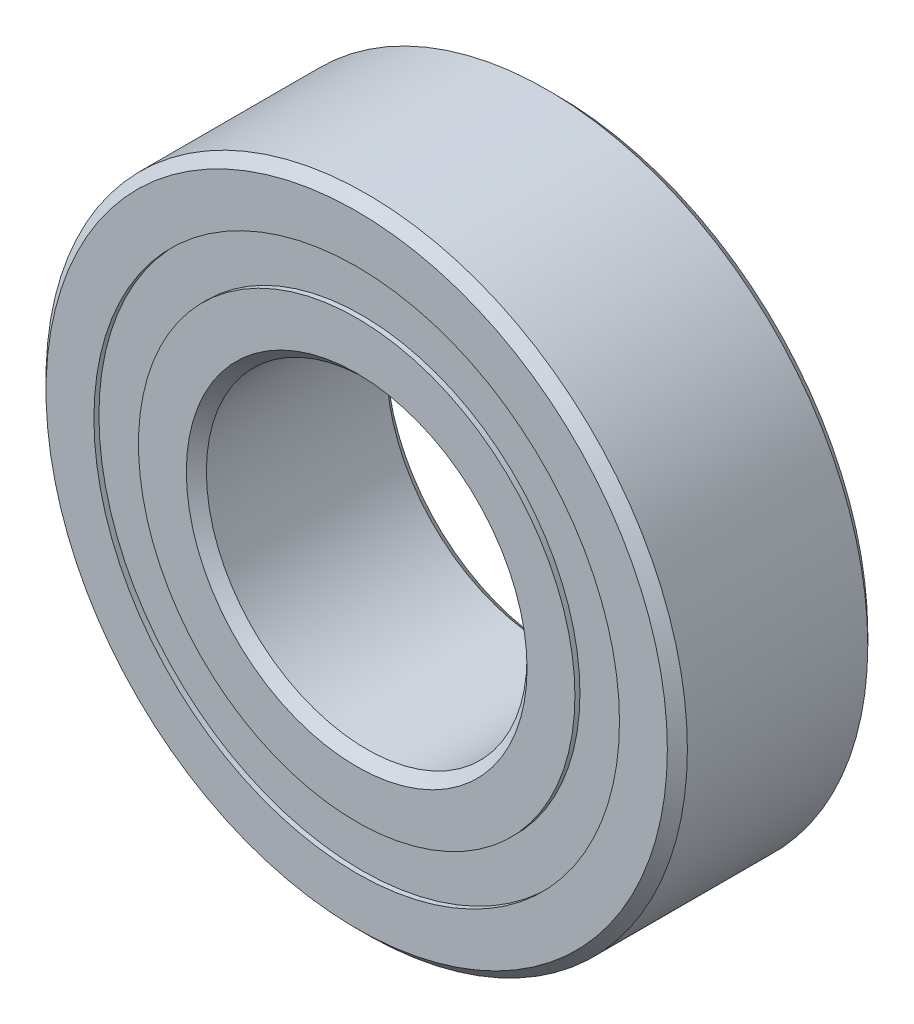
SolidWorks part; units mm, degrees
ref_plane "Front Plane" through (0, 0, 0) normal (0, 0, 1) x (1, 0, 0)
ref_plane "Top Plane" through (0, 0, 0) normal (0, 1, 0) x (1, 0, 0)
ref_plane "Right Plane" through (0, 0, 0) normal (1, 0, 0) x (0, 0, -1)
sketch "Sketch1" plane through (0, 0, 0) normal (1, 0, 0) x (0, 0, -1)
  line L0 (-2.5, 0) -> (2.5, 0) construction
  line L1 (0, 8) -> (0, -8) construction
  line L2 (2.25, 8) -> (-2.25, 8)
  line L3 (-2.25, 8) -> (-2.5, 7.75)
  line L4 (-2.5, 7.75) -> (-2.5, 6.5556)
  line L5 (-2.5, 6.5556) -> (-1.1111, 6.5556)
  line L6 (2.5, 6.5556) -> (1.1111, 6.5556)
  line L7 (2.5, 7.75) -> (2.5, 6.5556)
  line L8 (2.25, 8) -> (2.5, 7.75)
  line L9 (0, 8) -> (0, 6) construction
  line L10 (0, 6) -> (0, 4) construction
  arc A0 (-1.1111, 6.5556) -> (1.1111, 6.5556) centre (0, 6) cw
  arc A1 (-1.1111, 6.5556) -> (1.1111, 6.5556) centre (0, 6) ccw construction
  point P14 (0, 4)
  point P15 (0, -4)
  dimension "Width" = 5
  dimension "OD" = 16
  dimension "D1" = 45
  dimension "D2" = 0.25
  dimension "D3" = 2.2222
  dimension "Shaft Dia" = 8
  dimension "D4" = 0.5556
revolve "Revolve1" add sketch "Sketch1" angle 360 about L0
sketch "Sketch2" plane through (0, 0, 0) normal (1, 0, 0) x (0, 0, -1)
  line L0 (-2.5, 5.4444) -> (-1.1111, 5.4444)
  line L1 (-2.5, 7.75) -> (-2.5, -7.75) construction
  line L2 (-2.5, 5.4444) -> (-2.5, 4.25)
  line L3 (-2.5, 4.25) -> (-2.25, 4)
  line L4 (-2.25, 4) -> (2.25, 4)
  line L5 (0, 8) -> (0, -8) construction
  line L6 (0, 4) -> (0, 4.7577) construction
  line L7 (0, 4.7577) -> (0, 4) construction
  line L8 (-2.5, 5.4444) -> (-2.5, 3.0556) construction
  line L10 (2.5, 5.4444) -> (1.1111, 5.4444)
  line L11 (2.5, 5.4444) -> (2.5, 4.25)
  line L12 (2.5, 4.25) -> (2.25, 4)
  arc A0 (-1.1111, 5.4444) -> (1.1111, 5.4444) centre (0, 6) ccw
  arc A1 (1.1111, 6.5556) -> (-1.1111, 6.5556) centre (0, 6) ccw construction
  circle A2 centre (0, 6) radius 1.2423 construction
  dimension "D1" = 0.25
  dimension "D2" = 45
revolve "Revolve2" add sketch "Sketch2" angle 360 about L0
sketch "Sketch3" plane through (0, 0, 0) normal (1, 0, 0) x (0, 0, -1)
  line L0 (-1.2423, 6) -> (1.2423, 6)
  line L1 (0, 6) -> (0, 0) construction
  circle A1 centre (0, 6) radius 1.2423 construction
  arc A2 (-1.2423, 6) -> (1.2423, 6) centre (0, 6) cw
  arc A3 (1.1111, 6.5556) -> (-1.1111, 6.5556) centre (0, 6) ccw construction
  dimension "D1" = 2.4845
  dimension "D2" = 6
revolve "Revolve3" add sketch "Sketch3" angle 360 about L0
ref_axis "Axis1" through (0, 0, -2.5) along (0, 0, 1)
pattern_circular "CirPattern1" count 14 every 25.714 about axis through (0, 0, -2.5) along (0, 0, 1) of bodies 104
sketch "Sketch5" plane through (0, 0, 0) normal (1, 0, 0) x (0, 0, -1)
  line L0 (-2.5, 5.4444) -> (-1.1111, 5.4444) construction
  line L1 (-2.375, 6.5556) -> (-1.2423, 6.5556)
  line L2 (-2.375, 6.5556) -> (-2.375, 5.4444)
  line L3 (-2.375, 5.4444) -> (-1.2423, 5.4444)
  line L4 (-1.2423, 6.5556) -> (-1.2423, 5.4444)
  line L5 (1.2423, 6.5556) -> (2.375, 6.5556)
  line L6 (1.2423, 6.5556) -> (1.2423, 5.4444)
  line L7 (1.2423, 5.4444) -> (2.375, 5.4444)
  line L8 (2.375, 6.5556) -> (2.375, 5.4444)
  line L9 (-2.5, 6.5556) -> (-1.1111, 6.5556) construction
  line L10 (-2.375, 7.875) -> (-2.375, 6.5556) construction
  line L11 (-2.25, 8) -> (-2.5, 7.75) construction
  circle A0 centre (0, 6) radius 1.2423 construction
revolve "Revolve5" add sketch "Sketch5" angle 360 about L0
sketch "Sketch6" plane through (0, 0, 0) normal (0, 1, 0) x (1, 0, 0)
  point P0 (8, -2.5)
  point P1 (8, 2.5)
ref_axis "Center Axis 1" through (0, 0, -4.1209) along (0, 0, 1)
ref_plane "Contact Plane 1" through (0, 0, 2.5) normal (0, 0, 1) x (1, 0, 0)
ref_plane "Contact Plane 2" through (0, 0, -2.5) normal (0, 0, -1) x (-1, 0, 0)
equation "\"D2@Sketch1\" = \"Width@Sketch1\"*.05"
equation "\"D3@Sketch1\" = \"Width@Sketch1\"/2.25"
equation "\"D4@Sketch1\" = \"D3@Sketch1\"/4"
equation "\"Balls@CirPattern1\"=\"D2@Sketch3\"*2*pi/\"D1@Sketch3\"-1"
equation "\"D2@CirPattern1\" = 360/\"Balls@CirPattern1\""
equation "\"D1@Sketch2\"=\"D2@Sketch1\""
equation "\"D1@Sketch6\"=\"Width@Sketch1\""
